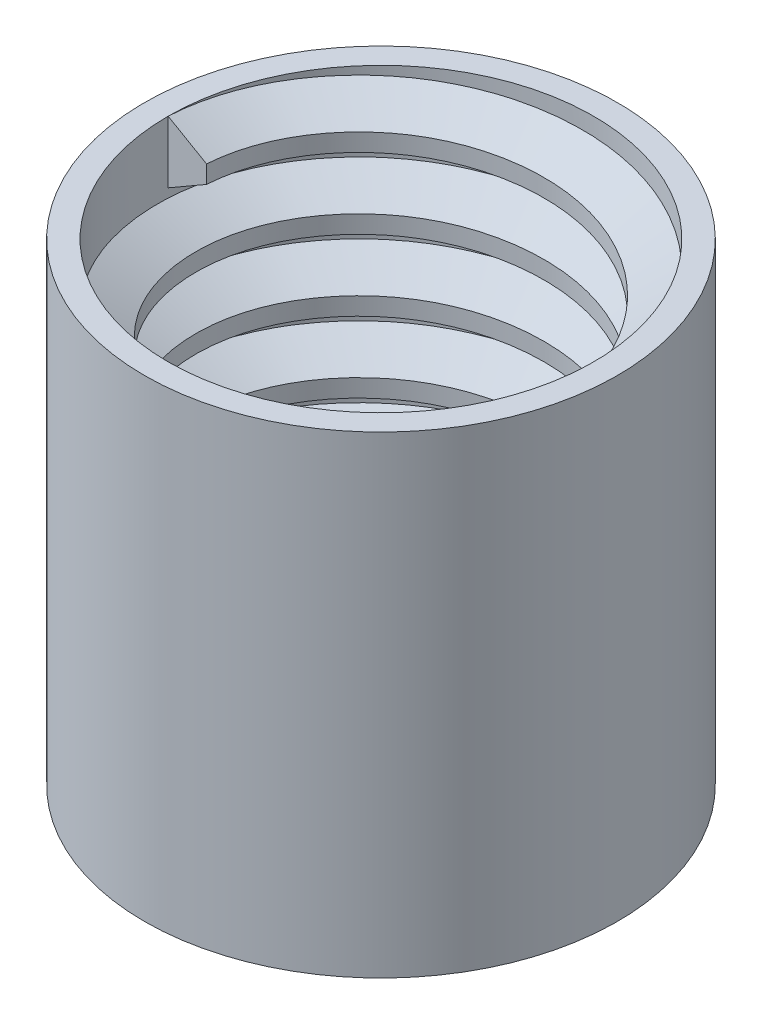
SolidWorks part; units mm, degrees
ref_plane "Front Plane" through (0, 0, 0) normal (0, 0, 1) x (1, 0, 0)
ref_plane "Top Plane" through (0, 0, 0) normal (0, 1, 0) x (1, 0, 0)
ref_plane "Right Plane" through (0, 0, 0) normal (1, 0, 0) x (0, 0, -1)
sketch "Sketch1" plane through (0, 0, 0) normal (0, 1, 0) x (1, 0, 0)
  circle A0 centre (0, 0) radius 5
  dimension "D1" = 10
extrude "Boss-Extrude1" add sketch "Sketch1" along normal blind 10
sketch "Sketch10" plane through (0, 10, 0) normal (0, 1, 0) x (1, 0, 0)
  circle A0 centre (0, 0) radius 4.5
  dimension "D1" = 9
extrude "Cut-Extrude2" cut sketch "Sketch10" against normal up to surface (10 mm away) up to face at (0, 0, 5)
thread "Thread2" pitch 1.5 method extrude profile "Thread Profile5" start angle 0, offset 0, length 0, pitch 1.5, diameter 9
ref_plane "Plane5" through (-4.5, 10, 0) normal (0, 0, 1) x (-1, 0, 0)
sketch "Thread Profile5" plane through (-4.5, 10, 0) normal (0, 0, 1) x (-1, 0, 0)
  line L0 (0, 0) -> (0, 1.5) construction
  line L11 (0, 0) -> (0, 1.3125)
  line L12 (0, 1.3125) -> (-0.8119, 0.8437)
  line L13 (-0.8119, 0.8437) -> (-0.8119, 0.4687)
  line L15 (-0.8119, 0.4687) -> (0, 0)
  line L17 (-0.8119, 0.6562) -> (0, 0.6562) construction
  point P2 (0, 0)
  dimension "Pitch" = 1.5
  dimension "Profile_Angle" = 60
  dimension "Profile_Land" = 0.375
  dimension "Profile_Height" = 0.8119
